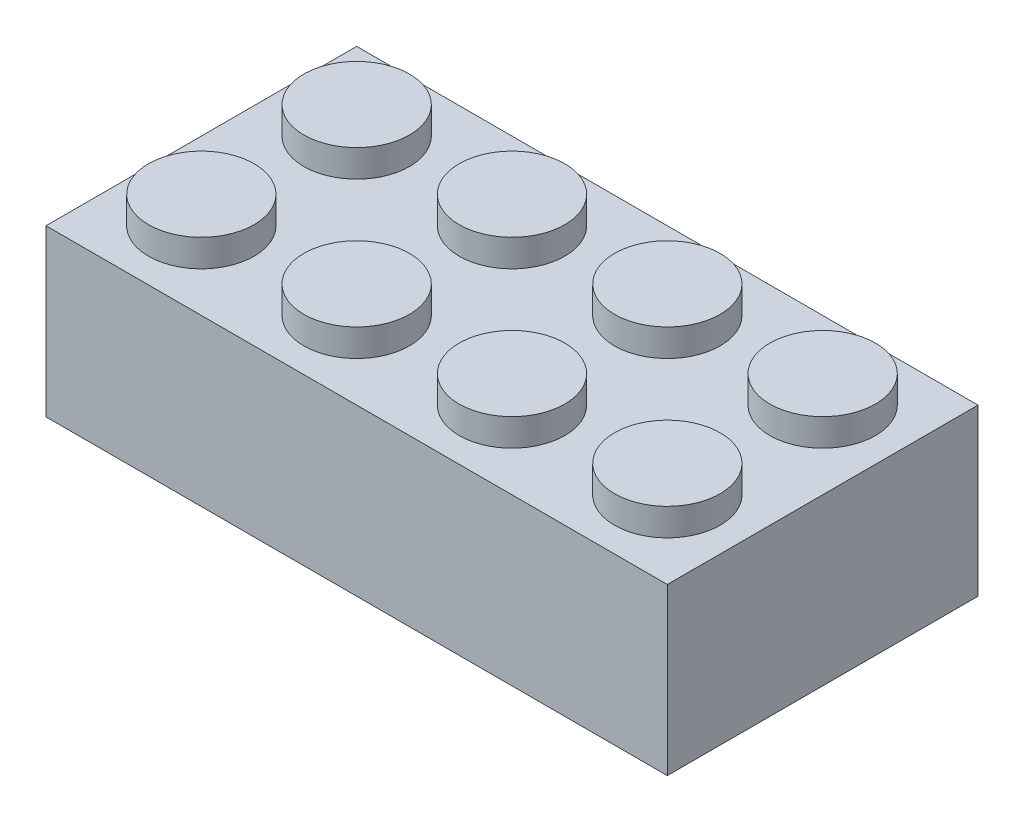
SolidWorks part; units mm, degrees
material "ABS"
ref_plane "Front Plane" through (0, 0, 0) normal (0, 0, 1) x (1, 0, 0)
ref_plane "Top Plane" through (0, 0, 0) normal (0, 1, 0) x (1, 0, 0)
ref_plane "Right Plane" through (0, 0, 0) normal (1, 0, 0) x (0, 0, -1)
sketch "Sketch1" plane through (0, 0, 0) normal (0, 1, 0) x (1, 0, 0)
  line L1 (-15.875, 7.9375) -> (15.875, 7.9375)
  line L2 (-15.875, 7.9375) -> (-15.875, -7.9375)
  line L3 (-15.875, -7.9375) -> (15.875, -7.9375)
  line L4 (15.875, 7.9375) -> (15.875, -7.9375)
  line L5 (-15.875, 7.9375) -> (15.875, -7.9375) construction
  line L6 (-15.875, -7.9375) -> (15.875, 7.9375) construction
  point P0 (0, 0)
  dimension "D1" = 15.875
  dimension "D2" = 31.75
extrude "Boss-Extrude1" add sketch "Sketch1" along normal mid plane 8.4582
sketch "Sketch2" plane through (0, -4.2291, 0) normal (0, -1, 0) x (1, 0, 0)
  line L12 (14.605, -6.6675) -> (14.605, 6.6675)
  line L13 (14.605, 6.6675) -> (-14.605, 6.6675)
  line L14 (-14.605, 6.6675) -> (-14.605, -6.6675)
  line L15 (-14.605, -6.6675) -> (14.605, -6.6675)
  line L16 (14.605, -6.6675) -> (14.605, 6.6675)
  line L17 (14.605, 6.6675) -> (-14.605, 6.6675)
  line L18 (-14.605, 6.6675) -> (-14.605, -6.6675)
  line L19 (-14.605, -6.6675) -> (14.605, -6.6675)
  circle A0 centre (0, 0) radius 3.175
  circle A1 centre (0, 0) radius 2.413
  dimension "D2" = 6.35
  dimension "D3" = 0.762
  dimension "D1" = 1.27
extrude "Cut-Extrude1" cut sketch "Sketch2" against normal offset from surface (7.1882 mm away) 1.27 contours L18 L19 L16 L17 A0 | A1 | A0 A1 region at (0, -4.2291, -6.3464) region at (-3.0852, -4.2291, 0) region at (0, -4.2291, 0) up to face at (0, 4.2291, 0)
sketch "Sketch3" plane through (0, 4.2291, 0) normal (0, 1, 0) x (1, 0, 0)
  line L0 (15.875, -7.9375) -> (15.875, 7.9375) construction
  line L1 (-15.875, -7.9375) -> (15.875, -7.9375) construction
  circle A0 centre (11.9063, -3.9688) radius 2.6987
  dimension "D3" = 5.3975
  dimension "D1" = 3.9688
  dimension "D2" = 3.9688
extrude "Boss-Extrude2" add sketch "Sketch3" along normal blind 1.397
pattern_linear "LPattern1" count 4 spacing 7.9375 along (-1, 0, 0) count 2 spacing 7.9375 along (0, 0, -1) of "Boss-Extrude2"
extrude "Boss-Extrude3" add sketch "Sketch2<3>" against normal up to surface (7.1882 mm away) contours A0 A1 region at (-3.0852, -4.2291, 0) up to face at (0, 2.9591, 0)
sketch "Sketch2<3>" plane through (0, -4.2291, 0) normal (0, -1, 0) x (1, 0, 0) same geometry as "Sketch2"
pattern_linear "LPattern2" count 2 spacing 7.9375 along (1, 0, 0) count 2 spacing 7.9375 along (-1, 0, 0) of "Boss-Extrude3"
